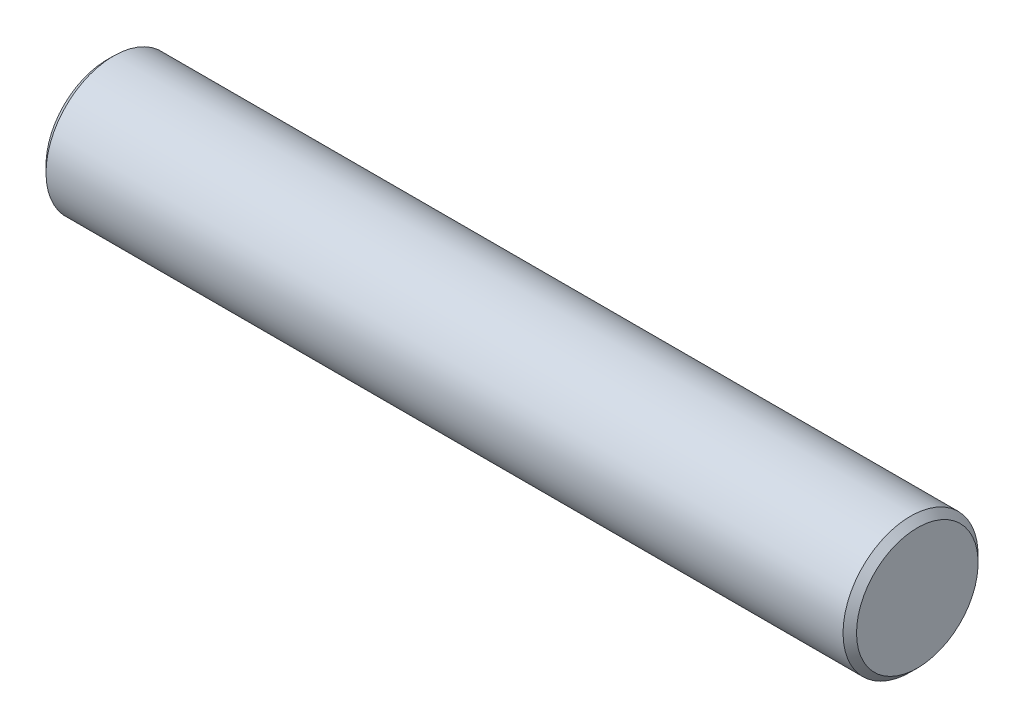
SolidWorks part; units mm, degrees
ref_plane "Front Plane" through (0, 0, 0) normal (0, 0, 1) x (1, 0, 0)
ref_plane "Top Plane" through (0, 0, 0) normal (0, 1, 0) x (1, 0, 0)
ref_plane "Right Plane" through (0, 0, 0) normal (1, 0, 0) x (0, 0, -1)
sketch "Sketch1" plane through (0, 0, 0) normal (0, 0, 1) x (1, 0, 0)
  line L0 (0, 0) -> (60, 0) construction
  line L1 (0, 0) -> (60, 0)
  line L2 (60, 0) -> (60, 5)
  line L3 (60, 5) -> (0, 5)
  line L4 (0, 5) -> (0, 0)
  dimension "L" = 60
  dimension "D" = 10
revolve "Revolve1" add sketch "Sketch1" angle 360 about L0
chamfer "Chamfer1" distance 0.5 angle 45 2 edges at (60, 0, 5) (0, 0, 5)
ref_plane "Plane1" through (0, 0, 5) normal (0, 0, 1) x (1, 0, 0)
ref_plane "Plane2" through (60, 0, 0) normal (1, 0, 0) x (0, 0, -1)
other "DeleteFace1" [suppressed]
chamfer "Chamfer2" [suppressed] distance 2 angle 45
ref_plane "Dim. KC" [suppressed] through (2, 0, 0) normal (1, 0, 0) x (0, 0, -1)
ref_plane "Plane3" [suppressed] through (2, 0, 0) normal (1, 0, 0) x (0, 0, -1)
ref_plane "Plane4" [suppressed] through (8, 0, 0) normal (1, 0, 0) x (0, 0, -1)
sketch "Sketch2" [suppressed] plane through (0, 0, 4) normal (0, 0, 1) x (1, 0, 0)
  line L0 (2, 0) -> (8, 0) construction
  line L1 (2, 1.5) -> (8, 1.5)
  line L2 (2, 1.5) -> (2, -1.5) construction
  line L3 (2, -1.5) -> (8, -1.5)
  line L4 (8, 1.5) -> (8, -1.5) construction
  line L5 (5, 1.5) -> (5, -1.5) construction
  line L6 (2, -4.4) -> (2, 4.4) construction
  line L7 (8, 1.5) -> (8, -1.5)
  line L8 (8, -4.4) -> (8, 4.4) construction
  line L9 (2, 1.5) -> (2, -1.5)
  line L12 (2, -4.4) -> (2, 4.4) construction
  dimension "A" = 6
  dimension "B_s" = 3
extrude "Boss-Extrude1" [suppressed] add sketch "Sketch2" against normal blind 1.8 separate body
fillet "Fillet1" [suppressed] type full round
fillet "Fillet2" [suppressed] type full round
sketch "Sketch3" [suppressed] plane through (0, 0, 4) normal (0, 0, 1) x (1, 0, 0)
  line L0 (9, 1.5) -> (9, -1.5) construction
  line L1 (6.5, 1.5) -> (11.5, 1.5)
  line L2 (6.5, 1.5) -> (6.5, -1.5)
  line L3 (6.5, -1.5) -> (11.5, -1.5)
  line L4 (11.5, 1.5) -> (11.5, -1.5)
  line L7 (6.5, 0) -> (11.5, 0) construction
  line L9 (10, 1.5) -> (10, -1.5) construction
  line L10 (8, 1.5) -> (8, -1.5) construction
  line L11 (2, 1.5) -> (8, 1.5) construction
  line L12 (2, -1.5) -> (8, -1.5) construction
  dimension "D1" = 1.5
  dimension "D2" = 2
  dimension "D3" = 1.5
extrude "Boss-Extrude2" [suppressed] add sketch "Sketch3" against normal blind 1.8
fillet "Fillet3" [suppressed] radius 0.1
other "DeleteFace2" [suppressed]
other "DeleteFace3" [suppressed]
combine bodies "Combine1" [suppressed] operation type subtract main body 101 bodies to subtract 146
ref_plane "KC_SEC1" [suppressed] through (5, 0, 0) normal (1, 0, 0) x (0, 0, -1)
ref_plane "KC_SEC2" [suppressed] through (9, 0, 0) normal (1, 0, 0) x (0, 0, -1)
ref_plane "Dim. WKC" [suppressed] through (2, 0, 0) normal (1, 0, 0) x (0, 0, -1)
ref_plane "Dim. K" [suppressed] through (20, 0, 0) normal (1, 0, 0) x (0, 0, -1)
ref_plane "Plane5" [suppressed] through (2, 0, 0) normal (1, 0, 0) x (0, 0, -1)
ref_plane "Plane6" [suppressed] through (20, 0, 0) normal (1, 0, 0) x (0, 0, -1)
sketch "Sketch4" [suppressed] plane through (0, 0, 4) normal (0, 0, 1) x (1, 0, 0)
  line L0 (2, 1.5) -> (2, -1.5)
  line L1 (2, 1.5) -> (8, 1.5)
  line L2 (2, 1.5) -> (2, -1.5) construction
  line L3 (2, -1.5) -> (8, -1.5)
  line L4 (8, 1.5) -> (8, -1.5)
  line L5 (2, -4.4) -> (2, 4.4) construction
  line L6 (2, -3.3) -> (2, 3.3) construction
  line L7 (8, 0) -> (2, 0) construction
  line L8 (5, 1.5) -> (5, -1.5) construction
  dimension "C" = 6
  dimension "B_s" = 3
extrude "Boss-Extrude3" [suppressed] add sketch "Sketch4" against normal blind 1.8 separate body
sketch "Sketch5" [suppressed] plane through (0, 0, 4) normal (0, 0, 1) x (1, 0, 0)
  line L0 (0, 0) -> (20, 0) construction
  line L2 (20, -3.3) -> (20, 3.3) construction
  line L4 (20, -3.3) -> (20, 3.3) construction
  line L5 (17, 1.5) -> (17, -1.5) construction
  line L9 (14, 1.5) -> (20, 1.5)
  line L10 (14, 1.5) -> (14, -1.5)
  line L11 (14, -1.5) -> (20, -1.5)
  line L12 (20, 1.5) -> (20, -1.5) construction
  line L13 (20, 1.5) -> (20, -1.5)
  dimension "B_s" = 3
  dimension "E" = 6
extrude "Boss-Extrude4" [suppressed] add sketch "Sketch5" against normal blind 1.8 separate body
sketch "Sketch6" [suppressed] plane through (0, 0, 4) normal (0, 0, 1) x (1, 0, 0)
  line L0 (2, 1.5) -> (8, 1.5) construction
  line L1 (6.5, 1.5) -> (11.5, 1.5)
  line L2 (6.5, 1.5) -> (6.5, -1.5)
  line L3 (6.5, -1.5) -> (11.5, -1.5)
  line L4 (11.5, 1.5) -> (11.5, -1.5)
  line L5 (2, -1.5) -> (8, -1.5) construction
  line L6 (8, 1.5) -> (8, -1.5) construction
  line L7 (9, 1.5) -> (9, -1.5) construction
  line L8 (10, 1.5) -> (10, -1.5) construction
  dimension "D1" = 1.5
  dimension "D2" = 2
  dimension "D3" = 1.5
extrude "Boss-Extrude5" [suppressed] add sketch "Sketch6" against normal blind 1.8
fillet "Fillet4" [suppressed] type full round
fillet "Fillet5" [suppressed] type full round
fillet "Fillet6" [suppressed] radius 0.1
fillet "Fillet7" [suppressed] type full round
fillet "Fillet8" [suppressed] type full round
fillet "Fillet9" [suppressed] radius 0.1
other "DeleteFace4" [suppressed]
other "DeleteFace5" [suppressed]
other "DeleteFace6" [suppressed]
other "DeleteFace7" [suppressed]
combine bodies "Combine2" [suppressed] operation type subtract main body 101 bodies to subtract 149 135
ref_plane "WKC_SEC1" [suppressed] through (5, 0, 0) normal (1, 0, 0) x (0, 0, -1)
ref_plane "WKC_SEC2" [suppressed] through (17, 0, 0) normal (1, 0, 0) x (0, 0, -1)
ref_plane "WKC_SEC3" [suppressed] through (9, 0, 0) normal (1, 0, 0) x (0, 0, -1)
ref_plane "Dim. KZ" [suppressed] through (2, 0, 0) normal (1, 0, 0) x (0, 0, -1)
ref_plane "Plane7" [suppressed] through (2, 0, 0) normal (1, 0, 0) x (0, 0, -1)
ref_plane "Plane8" [suppressed] through (8, 0, 0) normal (1, 0, 0) x (0, 0, -1)
sketch "Sketch7" [suppressed] plane through (0, 0, 4) normal (0, 0, 1) x (1, 0, 0)
  line L0 (0, 0) -> (8, 0) construction
  line L1 (2, 1.5) -> (8, 1.5)
  line L2 (2, 1.5) -> (2, -1.5) construction
  line L3 (2, -1.5) -> (8, -1.5)
  line L4 (8, 1.5) -> (8, -1.5) construction
  line L5 (2, -4.4) -> (2, 4.4) construction
  line L6 (2, -4.4) -> (2, 4.4) construction
  line L7 (2, 1.5) -> (2, -1.5)
  line L8 (8, 1.5) -> (8, -1.5)
  line L9 (8, -4.4) -> (8, 4.4) construction
  line L10 (5, 1.5) -> (5, -1.5) construction
  dimension "B_s" = 3
  dimension "Z" = 6
extrude "Boss-Extrude6" [suppressed] add sketch "Sketch7" against normal blind 1.8 separate body
fillet "Fillet10" [suppressed] type full round
fillet "Fillet11" [suppressed] type full round
sketch "Sketch8" [suppressed] plane through (0, 0, 4) normal (0, 0, 1) x (1, 0, 0)
  line L0 (1, 1.5) -> (1, -1.5) construction
  line L1 (-1.5, 1.5) -> (3.5, 1.5)
  line L2 (-1.5, 1.5) -> (-1.5, -1.5)
  line L3 (-1.5, -1.5) -> (3.5, -1.5)
  line L4 (3.5, 1.5) -> (3.5, -1.5)
  line L5 (2, 1.5) -> (2, -1.5) construction
  line L7 (-1.5, 0) -> (3.5, 0) construction
  line L9 (0, 1.5) -> (0, -1.5) construction
  line L10 (2, 1.5) -> (8, 1.5) construction
  line L11 (2, -1.5) -> (8, -1.5) construction
  dimension "D1" = 1.5
  dimension "D2" = 2
  dimension "D3" = 1.5
extrude "Boss-Extrude7" [suppressed] add sketch "Sketch8" against normal blind 1.8
fillet "Fillet12" [suppressed] radius 0.1
other "DeleteFace8" [suppressed]
other "DeleteFace9" [suppressed]
combine bodies "Combine3" [suppressed] operation type subtract main body 101 bodies to subtract 147
ref_plane "KZ_SEC1" [suppressed] through (5, 0, 0) normal (1, 0, 0) x (0, 0, -1)
ref_plane "KZ_SEC2" [suppressed] through (1, 0, 0) normal (1, 0, 0) x (0, 0, -1)
ref_plane "Dim. FC" [suppressed] through (1, 0, 0) normal (1, 0, 0) x (0, 0, -1)
sketch "Sketch9" [suppressed] plane through (0, 0, 0) normal (0, 1, 0) x (1, 0, 0)
  line L0 (0, 0) -> (2, 0) construction
  line L1 (1, -3) -> (2, -3)
  line L2 (1, -3) -> (1, -4)
  line L3 (1, -4) -> (2, -4)
  line L4 (2, -3) -> (2, -4)
  line L5 (1, -3.3) -> (1, 3.3) construction
  line L6 (1.5, -4) -> (1.5, -3) construction
  dimension "G" = 1
  dimension "H" = 1
  dimension "D" = 10
extrude "Cut-Extrude1" [suppressed] cut sketch "Sketch9" against normal through all and the other way through all
ref_plane "FC_SEC" [suppressed] through (1.5, 0, 0) normal (1, 0, 0) x (0, 0, -1)
ref_plane "Dim. WFC" [suppressed] through (1, 0, 0) normal (1, 0, 0) x (0, 0, -1)
ref_plane "Dim. W" [suppressed] through (19, 0, 0) normal (1, 0, 0) x (0, 0, -1)
sketch "Sketch10" [suppressed] plane through (0, 0, 0) normal (0, 1, 0) x (1, 0, 0)
  line L0 (0, 0) -> (19, 0) construction
  line L1 (1, -4) -> (2, -4)
  line L2 (1, -4) -> (1, -3)
  line L3 (1, -3) -> (2, -3)
  line L4 (2, -4) -> (2, -3)
  line L5 (1.5, -3) -> (1.5, -4) construction
  line L6 (19, -4) -> (18, -4)
  line L7 (19, -4) -> (19, -3)
  line L8 (19, -3) -> (18, -3)
  line L9 (18, -4) -> (18, -3)
  line L10 (1, -3.3) -> (1, 3.3) construction
  line L11 (19, -3.3) -> (19, 3.3) construction
  line L12 (18.5, -3) -> (18.5, -4) construction
  dimension "J" = 1
  dimension "V" = 1
  dimension "H" = 1
  dimension "D" = 10
  dimension "H_s_R" = 1
extrude "Cut-Extrude2" [suppressed] cut sketch "Sketch10" against normal through all and the other way through all
ref_plane "WFC_SEC1" [suppressed] through (1.5, 0, 0) normal (1, 0, 0) x (0, 0, -1)
ref_plane "WFC_SEC2" [suppressed] through (18.5, 0, 0) normal (1, 0, 0) x (0, 0, -1)
ref_plane "Dim. SFC" [suppressed] through (1, 0, 0) normal (1, 0, 0) x (0, 0, -1)
sketch "Sketch11" [suppressed] plane through (0, 0, 0) normal (0, 1, 0) x (1, 0, 0)
  line L0 (0, 0) -> (2, 0) construction
  line L1 (1, -4) -> (2, -4)
  line L2 (1, -4) -> (1, -3)
  line L3 (1, -3) -> (2, -3)
  line L4 (2, -4) -> (2, -3)
  line L5 (1, -3.3) -> (1, 3.3) construction
  line L6 (1.5, -3) -> (1.5, -4) construction
  dimension "SG" = 1
  dimension "H" = 1
  dimension "D" = 10
extrude "Cut-Extrude3" [suppressed] cut sketch "Sketch11" against normal through all and the other way through all
pattern_circular "CirPattern1" [suppressed] count 2 every 120 of bodies 119
ref_plane "Plane9" [suppressed] through (0, 0, 0) normal (0, -0.5, 0.866) x (1, 0, 0)
sketch "Sketch12" [suppressed] plane through (0, 0, 0) normal (0, -0.5, 0.866) x (1, 0, 0)
  line L0 (0, 0) -> (2, 0) construction
  line L2 (1, -3) -> (2, -3)
  line L3 (1, -3) -> (1, -4)
  line L4 (1, -4) -> (2, -4)
  line L5 (2, -3) -> (2, -4)
  line L6 (1, -3.3) -> (1, 3.3) construction
  dimension "D" = 10
  dimension "SG" = 1
  dimension "H" = 1
ref_plane "SFC_SEC" [suppressed] through (1.5, 0, 0) normal (1, 0, 0) x (0, 0, -1)
sketch "Sketch13" [suppressed] plane through (1.5, 0, 0) normal (1, 0, 0) x (0, 0, -1)
  line L0 (-4, 0) -> (-3, 0) construction
  line L1 (-3, 0) -> (-4, 0) construction
  line L2 (2, -3.4641) -> (1.5, -2.5981) construction
  line L3 (1.5, -2.5981) -> (2, -3.4641) construction
  line L4 (1.5, -2.5981) -> (2, -3.4641) construction
  dimension "ANG" = 120
sketch "Sketch14" [suppressed] plane through (0, 0, 0) normal (0, 1, 0) x (1, 0, 0)
  line L0 (0, 0) -> (20, 0) construction
  line L1 (1.5, 4) -> (1.5, 3.5) construction
  line L2 (0, 3.5) -> (3, 3.5)
  line L3 (0, 3.5) -> (0, 4)
  line L4 (0, 4) -> (3, 4)
  line L5 (3, 3.5) -> (3, 4)
  line L6 (17, 3.5) -> (20, 3.5)
  line L7 (17, 3.5) -> (17, 4)
  line L8 (17, 4) -> (20, 4)
  line L9 (20, 3.5) -> (20, 4)
  line L10 (0, -4) -> (3, -4)
  line L11 (0, -4) -> (0, -3.5)
  line L12 (0, -3.5) -> (3, -3.5)
  line L13 (3, -4) -> (3, -3.5)
  line L14 (17, -4) -> (20, -4)
  line L15 (17, -4) -> (17, -3.5)
  line L16 (17, -3.5) -> (20, -3.5)
  line L17 (20, -4) -> (20, -3.5)
  line L18 (1.5, -3.5) -> (1.5, -4) construction
  line L19 (18.5, 4) -> (18.5, 3.5) construction
  line L20 (18.5, -3.5) -> (18.5, -4) construction
  dimension "D" = 10
  dimension "W_1" = 7
  dimension "KWC" = 3
  dimension "KWC_L1" = 3
  dimension "KWC_R1" = 3
  dimension "KWC_R2" = 3
  dimension "W_1_R" = 7
extrude "Cut-Extrude4" [suppressed] cut sketch "Sketch14" against normal through all and the other way through all
ref_plane "KWC_SEC1" [suppressed] through (1.5, 0, 0) normal (1, 0, 0) x (0, 0, -1)
ref_plane "KWC_SEC2" [suppressed] through (18.5, 0, 0) normal (1, 0, 0) x (0, 0, -1)
sketch "Sketch15" [suppressed] plane through (0, 0, 0) normal (0, 1, 0) x (1, 0, 0)
  line L0 (0, 0) -> (20, 0) construction
  line L1 (1.5, -3) -> (1.5, -4) construction
  line L2 (0, 3) -> (3, 3)
  line L3 (0, 3) -> (0, 4)
  line L4 (0, 4) -> (3, 4)
  line L5 (3, 3) -> (3, 4)
  line L6 (17, 3) -> (20, 3)
  line L7 (17, 3) -> (17, 4)
  line L8 (17, 4) -> (20, 4)
  line L9 (20, 3) -> (20, 4)
  line L10 (0, -4) -> (3, -4)
  line L11 (0, -4) -> (0, -3)
  line L12 (0, -3) -> (3, -3)
  line L13 (3, -4) -> (3, -3)
  line L14 (17, -4) -> (20, -4)
  line L15 (17, -4) -> (17, -3)
  line L16 (17, -3) -> (20, -3)
  line L17 (20, -4) -> (20, -3)
  line L18 (18.5, -3) -> (18.5, -4) construction
  dimension "D" = 10
  dimension "KWC_L1" = 3
  dimension "KWC_R1" = 3
  dimension "WC" = 6
  dimension "KWC" = 3
  dimension "KWC_R2" = 3
  dimension "WC_R" = 6
extrude "Cut-Extrude5" [suppressed] cut sketch "Sketch15" against normal through all and the other way through all
ref_plane "WC_SEC1" [suppressed] through (1.5, 0, 0) normal (1, 0, 0) x (0, 0, -1)
ref_plane "WC_SEC2" [suppressed] through (18.5, 0, 0) normal (1, 0, 0) x (0, 0, -1)
sketch "Sketch16" [suppressed] plane through (0, 0, 0) normal (0, 0, 1) x (1, 0, 0)
  line L0 (20, 4) -> (0, 4) construction
  line L1 (1.1, 3.5) -> (2, 3.5)
  line L2 (1.1, 3.5) -> (1.1, 4)
  line L3 (1.1, 4) -> (2, 4)
  line L4 (2, 3.5) -> (2, 4)
  line L5 (0, 0) -> (2, 0) construction
  line L6 (0, 4) -> (0, 0) construction
  dimension "D_s_1" = 7
  dimension "M_s" = 0.9
  dimension "TA" = 2
revolve "Cut-Revolve1" [suppressed] cut sketch "Sketch16" angle 360 about L5
sketch "Sketch17" [suppressed] plane through (0, 0, 0) normal (0, 0, 1) x (1, 0, 0)
  line L1 (18, 3.5) -> (18.9, 3.5)
  line L2 (18, 3.5) -> (18, 4)
  line L3 (18, 4) -> (18.9, 4)
  line L4 (18.9, 3.5) -> (18.9, 4)
  line L5 (0, 0) -> (20, 0) construction
  line L7 (20, -3.3) -> (20, 3.3) construction
  dimension "D_s_1" = 7
  dimension "M_s" = 0.9
  dimension "D" = 10
  dimension "TB" = 2
revolve "Cut-Revolve2" [suppressed] cut sketch "Sketch17" angle 360 about L5
sketch "Sketch18" [suppressed] plane through (0, 0, 0) normal (0, 0, 1) x (1, 0, 0)
  line L0 (0, 0) -> (20, 0) construction
  line L1 (0, 4) -> (0, -4) construction
  line L3 (1, 4) -> (5, 4)
  line L4 (1, 4) -> (1, 3.5)
  line L5 (1, 3.5) -> (5, 3.5)
  line L6 (5, 4) -> (5, 3.5)
  line L7 (20, 4) -> (0, 4) construction
  line L8 (20, -3.3) -> (20, 3.3) construction
  dimension "D_s_2" = 7
  dimension "UC" = 1
  dimension "L1_s" = 4
revolve "Cut-Revolve3" [suppressed] cut sketch "Sketch18" angle 360 about L0
ref_plane "Dim. SC" [suppressed] through (2, 0, 0) normal (1, 0, 0) x (0, 0, -1)
sketch "Sketch19" [suppressed] plane through (0, 0, 0) normal (0, 1, 0) x (1, 0, 0)
  line L0 (20, -3.3) -> (20, 3.3) construction
  line L1 (2, -3.5) -> (10, -3.5)
  line L2 (2, -3.5) -> (2, -4)
  line L3 (2, -4) -> (10, -4)
  line L4 (10, -3.5) -> (10, -4)
  line L5 (2, 4) -> (10, 4)
  line L6 (2, 4) -> (2, 3.5)
  line L7 (2, 3.5) -> (10, 3.5)
  line L8 (10, 4) -> (10, 3.5)
  line L9 (6, 4) -> (6, 3.5) construction
  line L10 (6, -3.5) -> (6, -4) construction
  line L12 (0, 0) -> (20, 0) construction
  line L14 (2, -3.3) -> (2, 3.3) construction
  dimension "W_2" = 7
  dimension "L2_s" = 8
  dimension "D" = 10
  dimension "L2_s_L1" = 8
extrude "Cut-Extrude6" [suppressed] cut sketch "Sketch19" against normal through all and the other way through all
ref_plane "SC_SEC" [suppressed] through (6, 0, 0) normal (1, 0, 0) x (0, 0, -1)
equation "\"Plane dim\"= \"D@Sketch1\" * 0.5"
equation "\"D1@Plane3\"= if ( \"KC@Dim. KC\" < 1 , 0 , \"KC@Dim. KC\" )"
equation "\"D1@Plane4\" = if ( \"KC@Dim. KC\" > \"L@Sketch1\" - \"A@Sketch2\" - 1 , \"L@Sketch1\" , \"KC@Dim. KC\" + \"A@Sketch2\" )"
equation "\"D1@Plane5\"=if ( \"WKC@Dim. WKC\" < 1 , 0 , \"WKC@Dim. WKC\" )"
equation "\"D1@Plane6\"=if ( \"K@Dim. K\" < 1 , 0 , \"K@Dim. K\" )"
equation "\"D1@Plane7\"=if ( \"KZ@Dim. KZ\" < 1 , 0 , \"KZ@Dim. KZ\" )"
equation "\"D1@Plane8\"=if ( \"KZ@Dim. KZ\" > \"L@Sketch1\" - \"Z@Sketch7\" - 1 , \"L@Sketch1\", \"KZ@Dim. KZ\" + \"Z@Sketch7\" )"
equation "\"D1@Sketch3\"=\"B_s@Sketch2\"/2"
equation "\"D3@Sketch3\"=\"B_s@Sketch2\"/2"
equation "\"D1@Sketch8\"=\"B_s@Sketch7\"/2"
equation "\"D3@Sketch8\"=\"B_s@Sketch7\"/2"
equation "\"D1@Sketch6\"=\"B_s@Sketch4\"/2"
equation "\"D3@Sketch6\"=\"B_s@Sketch4\"/2"
equation "\"D@Sketch12\" = \"D@Sketch11\""
equation "\"SG@Sketch12\" = \"SG@Sketch11\""
equation "\"H@Sketch12\"= \"H@Sketch11\""
